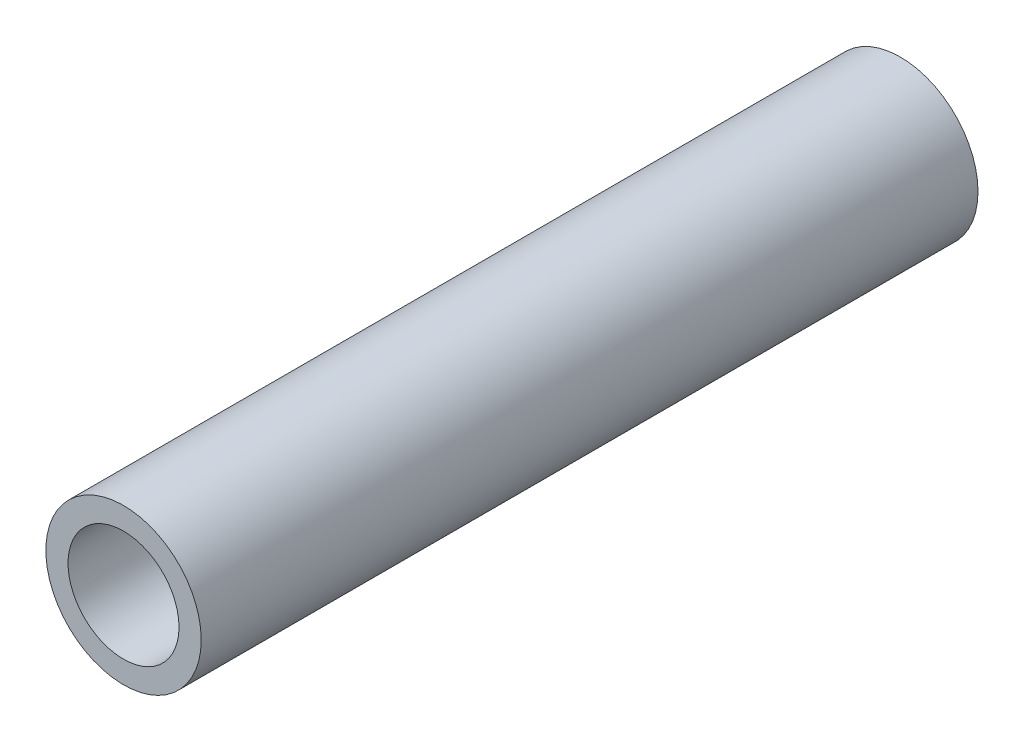
SolidWorks part; units mm, degrees
material "Lega 1060"
ref_plane "Piano frontale" through (0, 0, 0) normal (0, 0, 1) x (1, 0, 0)
ref_plane "Piano superiore" through (0, 0, 0) normal (0, 1, 0) x (1, 0, 0)
ref_plane "Piano destro" through (0, 0, 0) normal (1, 0, 0) x (0, 0, -1)
sketch "Schizzo1" plane through (0, 0, 0) normal (0, 0, 1) x (1, 0, 0)
  circle A0 centre (0, 0) radius 70
  circle A1 centre (0, 0) radius 50
  dimension "D1" = 140
  dimension "D2" = 100
extrude "Estrusione-Estrusione1" add sketch "Schizzo1" along normal blind 700
